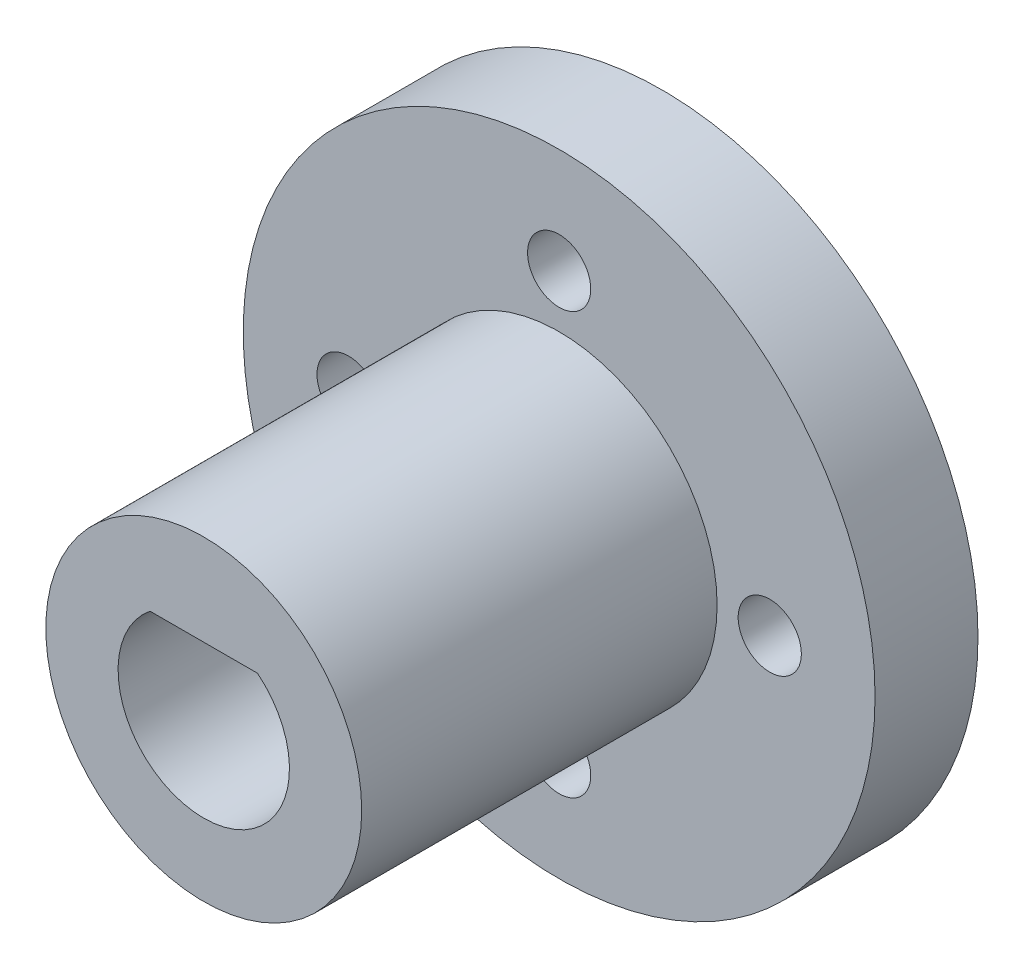
SolidWorks part; units mm, degrees
ref_plane "Plan de face" through (0, 0, 0) normal (0, 0, 1) x (1, 0, 0)
ref_plane "Plan de dessus" through (0, 0, 0) normal (0, 1, 0) x (1, 0, 0)
ref_plane "Plan de droite" through (0, 0, 0) normal (1, 0, 0) x (0, 0, -1)
sketch "Esquisse1" plane through (0, 0, 0) normal (0, 0, 1) x (1, 0, 0)
  circle A0 centre (0, 0) radius 12
  dimension "D1" = 24
extrude "Boss.-Extru.1" add sketch "Esquisse1" along normal blind 3.91
sketch "Esquisse6" plane through (0, 0, 0) normal (0, 0, -1) x (-1, 0, 0)
  circle A0 centre (0, 0) radius 4.15
  dimension "D1" = 8.3
extrude "Enlèv. mat.-Extru.2" cut sketch "Esquisse6" against normal blind 2.5
sketch "Esquisse7" plane through (0, 0, 3.91) normal (0, 0, 1) x (1, 0, 0)
  line L0 (2.0418, 2.535) -> (-2.0418, 2.535)
  line L1 (-5.4714, -3.255) -> (6.192, -3.255) construction
  arc A0 (-2.0418, 2.535) -> (2.0418, 2.535) centre (0, 0) ccw
  circle A1 centre (0, 0) radius 6
  dimension "D1" = 6.51
  dimension "D3" = 12
  dimension "D2" = 5.79
extrude "Boss.-Extru.2" add sketch "Esquisse7" along normal blind 13.5 contours A1 L1 A0 L0 | L1 A1 region at (-2.5202, -3.1035, 3.91) region at (0, -4.3779, 3.91)
hole_wizard "Dégagement M21" positions "Esquisse10" profile "Esquisse11" hole size "M2" standard "Ansi Metric" end condition through all
sketch "Esquisse10" plane through (0, 0, 3.91) normal (0, 0, 1) x (1, 0, 0)
  point P0 (0, 8)
  dimension "D1" = 8
sketch "Esquisse11" plane through (0, 8, 3.91) normal (1, 0, 0) x (0, -1, 0)
  line L0 (0, 0) -> (0, 3.91)
  line L1 (0, 3.91) -> (1.2, 3.91)
  line L2 (1.2, 3.91) -> (1.2, 0)
  line L5 (1.2, 0) -> (0, 0)
  line L11 (0, -6.35) -> (0, 107.95) construction
  dimension "Diamètre du perçage jusqu'au prochain" = 2.4
  dimension "Profondeur du perçage jusqu'au prochain" = 3.91
pattern_circular "Répétition circulaire2" count 4 every 90 about axis through (0, 0, 3.91) along (0, 0, 1) of "Dégagement M21"
